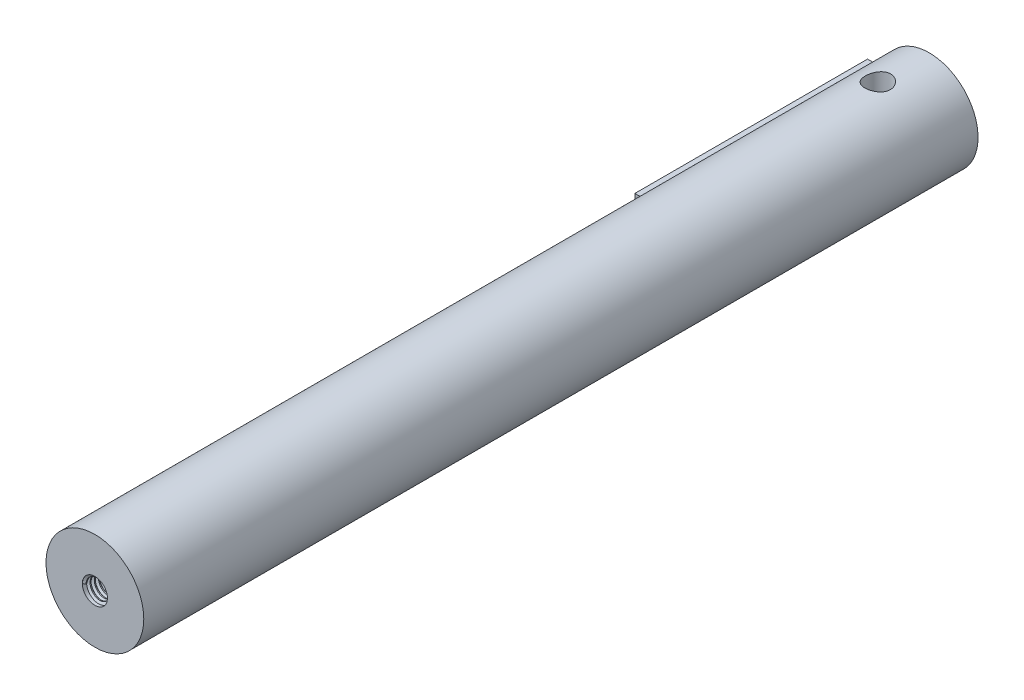
SolidWorks part; units mm, degrees
ref_plane "Front Plane" through (0, 0, 0) normal (0, 0, 1) x (1, 0, 0)
ref_plane "Top Plane" through (0, 0, 0) normal (0, 1, 0) x (1, 0, 0)
ref_plane "Right Plane" through (0, 0, 0) normal (1, 0, 0) x (0, 0, -1)
sketch "Sketch1" plane through (0, 0, 0) normal (0, 0, 1) x (1, 0, 0)
  line L0 (0, 0) -> (0, 3.175)
  line L1 (0, 3.175) -> (-15.621, 3.175)
  line L2 (-15.621, 3.175) -> (-15.621, -2.921)
  line L3 (-15.621, -2.921) -> (0, -2.921)
  line L4 (0, -2.921) -> (0, 0)
  circle A0 centre (0, 0) radius 12.3825
  dimension "D1" = 24.765
  dimension "D2" = 6.096
  dimension "D3" = 3.175
  dimension "D4" = 15.621
extrude "Boss-Extrude4" add sketch "Sketch1" along normal blind 58.928 contours L3 A0 L1 L0 L4 | L1 A0 L3 L4 L0 | A0 L1 L2 L3 region at (-6.1283, 0.1244, 0) region at (1.125, -0.0228, 0) region at (-13.9364, 0.1366, 0)
sketch "Sketch8" plane through (0, 0, 58.928) normal (0, 0, 1) x (1, 0, 0)
  circle A0 centre (0, 0) radius 12.3825
  dimension "D1" = 24.765
extrude "Boss-Extrude5" add sketch "Sketch8" along normal blind 152.4
sketch "Sketch10" plane through (0, 0, 211.328) normal (0, 0, 1) x (1, 0, 0)
  circle A0 centre (0, 0) radius 3.175
  dimension "D1" = 6.35
extrude "Cut-Extrude1" cut sketch "Sketch10" against normal blind 12.7
thread "Thread1" pitch 1.0583 method extrude profile "Thread Profile1" start angle 0, offset 0, length 0, pitch 1.0583, diameter 6.35
ref_plane "Plane1" through (-3.175, 0, 211.328) normal (0, -1, 0) x (-1, 0, 0)
sketch "Thread Profile1" plane through (-3.175, 0, 211.328) normal (0, -1, 0) x (-1, 0, 0)
  line L0 (0, 0) -> (0, 1.0583) construction
  line L11 (0, 0) -> (0, 0.926)
  line L12 (0, 0.926) -> (-0.5728, 0.5953)
  line L13 (-0.5728, 0.5953) -> (-0.5728, 0.3307)
  line L15 (-0.5728, 0.3307) -> (0, 0)
  line L17 (-0.5728, 0.463) -> (0, 0.463) construction
  point P2 (0, 0)
  dimension "Pitch" = 1.0583
  dimension "Profile_Angle" = 60
  dimension "Profile_Land" = 0.2646
  dimension "Profile_Height" = 0.5728
sketch "Sketch11" plane through (0, 0, 0) normal (0, 1, 0) x (1, 0, 0)
  line L0 (12.3825, 0) -> (-12.033, 0) construction
  line L1 (12.3825, -211.328) -> (12.3825, 0) construction
  circle A0 centre (-0.3175, -12.7) radius 3.175
  dimension "D1" = 6.35
  dimension "D2" = 12.7
  dimension "D3" = 12.7
extrude "Cut-Extrude2" cut sketch "Sketch11" against normal through all and the other way through all
